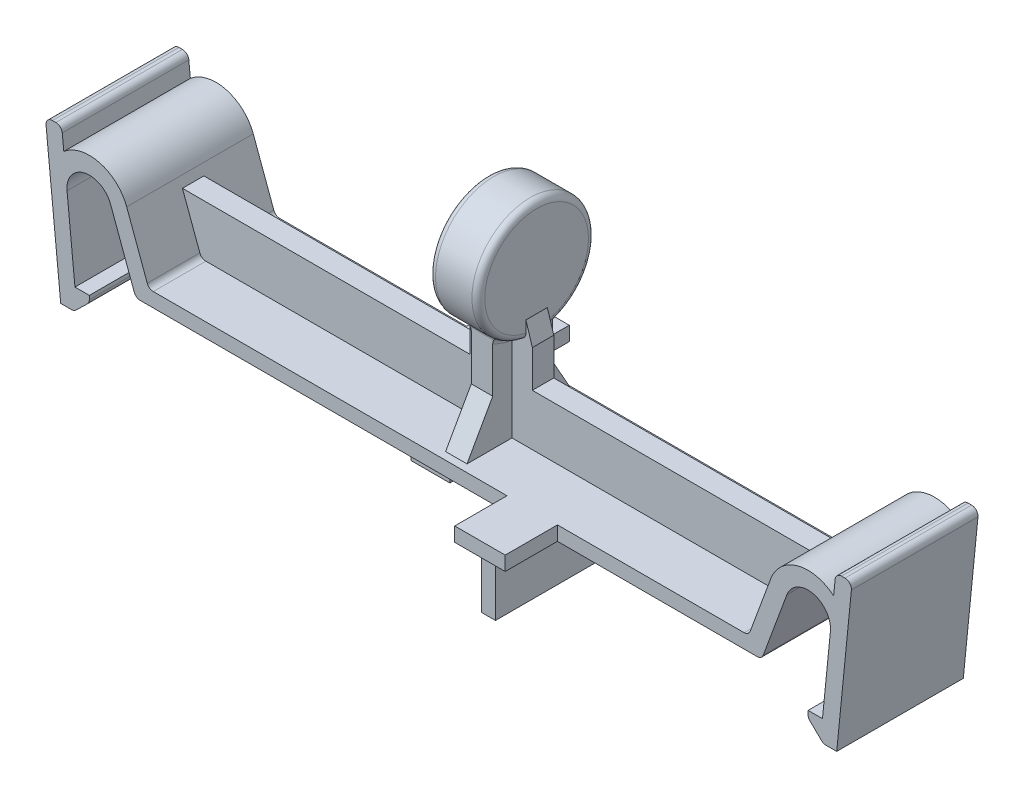
SolidWorks part; units mm, degrees
ref_plane "Front Plane" through (0, 0, 0) normal (0, 0, 1) x (1, 0, 0)
ref_plane "Top Plane" through (0, 0, 0) normal (0, 1, 0) x (1, 0, 0)
ref_plane "Right Plane" through (0, 0, 0) normal (1, 0, 0) x (0, 0, -1)
sketch "Sketch2" plane through (0, 0, 0) normal (0, 0, 1) x (1, 0, 0)
  line L3 (-37.5805, 8.6675) -> (-35.1807, 2.1508)
  line L4 (-34.477, 1.66) -> (34.477, 1.66)
  line L6 (35.997, 0) -> (-35.997, 0)
  line L7 (-36.7007, 0.4908) -> (-39.4573, 7.9764)
  line L12 (0, 0) -> (0, 8.4417) construction
  line L13 (-44.542, 6.8066) -> (-43.6179, -2.46)
  line L14 (-43.6179, -2.46) -> (-41.94, -2.46)
  line L15 (-41.94, -2.46) -> (-41.94, -2.8931)
  line L16 (-42.1673, -3.4309) -> (-43.5017, -4.7278)
  line L17 (-44.0244, -4.94) -> (-45.28, -4.94)
  line L18 (-45.28, -4.94) -> (-46.9928, 12.2356)
  line L19 (-46.2465, 13.06) -> (-45.8445, 13.06)
  line L20 (-45.0982, 12.3844) -> (-44.9201, 10.5982)
  line L21 (45.0982, 12.3844) -> (44.9201, 10.5982)
  line L22 (46.2465, 13.06) -> (45.8445, 13.06)
  line L23 (45.28, -4.94) -> (46.9928, 12.2356)
  line L24 (44.0244, -4.94) -> (45.28, -4.94)
  line L25 (42.1673, -3.4309) -> (43.5017, -4.7278)
  line L26 (41.94, -2.46) -> (41.94, -2.8931)
  line L27 (43.6179, -2.46) -> (41.94, -2.46)
  line L28 (44.542, 6.8066) -> (43.6179, -2.46)
  line L29 (36.7007, 0.4908) -> (39.4573, 7.9764)
  line L30 (37.5805, 8.6675) -> (35.1807, 2.1508)
  arc A1 (-39.4573, 7.9764) -> (-44.542, 6.8066) centre (-41.9251, 7.0676) ccw
  arc A2 (-44.9201, 10.5982) -> (-37.5805, 8.6675) centre (-41.9251, 7.0676) cw
  arc A3 (-41.94, -2.8931) -> (-42.1673, -3.4309) centre (-42.69, -2.8931) cw
  arc A4 (-43.5017, -4.7278) -> (-44.0244, -4.94) centre (-44.0244, -4.19) cw
  arc A5 (-35.997, 0) -> (-36.7007, 0.4908) centre (-35.997, 0.75) cw
  arc A6 (-35.1807, 2.1508) -> (-34.477, 1.66) centre (-34.477, 2.41) ccw
  arc A7 (-45.8445, 13.06) -> (-45.0982, 12.3844) centre (-45.8445, 12.31) cw
  arc A8 (-46.9928, 12.2356) -> (-46.2465, 13.06) centre (-46.2465, 12.31) cw
  arc A9 (46.9928, 12.2356) -> (46.2465, 13.06) centre (46.2465, 12.31) ccw
  arc A10 (45.8445, 13.06) -> (45.0982, 12.3844) centre (45.8445, 12.31) ccw
  arc A11 (35.1807, 2.1508) -> (34.477, 1.66) centre (34.477, 2.41) cw
  arc A12 (35.997, 0) -> (36.7007, 0.4908) centre (35.997, 0.75) ccw
  arc A13 (43.5017, -4.7278) -> (44.0244, -4.94) centre (44.0244, -4.19) ccw
  arc A14 (41.94, -2.8931) -> (42.1673, -3.4309) centre (42.69, -2.8931) ccw
  arc A15 (44.9201, 10.5982) -> (37.5805, 8.6675) centre (41.9251, 7.0676) ccw
  arc A16 (39.4573, 7.9764) -> (44.542, 6.8066) centre (41.9251, 7.0676) cw
  point P22 (-41.94, -3.21)
  point P25 (-43.72, -4.94)
  point P28 (-36.52, 0)
  point P31 (-35, 1.66)
  point P36 (-47.075, 13.06)
  point P63 (0, 1.66)
  dimension "D15" = 0.75
  dimension "D1" = 1.66
  dimension "D2" = 70
  dimension "D3" = 2
  dimension "D4" = 8.5
  dimension "D5" = 73.04
  dimension "D6" = 90.56
  dimension "D7" = 3.34
  dimension "D8" = 2.48
  dimension "D9" = 4.94
  dimension "D10" = 0.75
  dimension "D11" = 1.78
  dimension "D12" = 94.15
  dimension "D13" = 18
  dimension "D14" = 1.9
extrude "Boss-Extrude1" add sketch "Sketch2" along normal mid plane 14.77
sketch "Sketch3" plane through (0, 0, 0) normal (1, 0, 0) x (0, 0, -1)
  line L0 (-7.385, 1.66) -> (7.385, 1.66) construction
  line L1 (-1.25, 1.66) -> (1.25, 1.66)
  line L2 (-1.25, 1.66) -> (-1.25, 7.66)
  line L3 (-1.25, 7.66) -> (1.25, 7.66)
  line L4 (1.25, 1.66) -> (1.25, 7.66)
  line L5 (0, 0) -> (0, 7.66) construction
  dimension "D1" = 2.5
  dimension "D2" = 6
extrude "Boss-Extrude2" add sketch "Sketch3" along normal up to next and the other way up to next
sketch "Sketch4" plane through (0, 0, 0) normal (1, 0, 0) x (0, 0, -1)
  line L0 (-6.5, 1.66) -> (-3.5, 7)
  line L1 (-7.385, 1.66) -> (-1.25, 1.66) construction
  line L2 (-3.5, 7) -> (-3.5, 15.66)
  line L3 (-3.5, 15.66) -> (3.5, 15.66)
  line L4 (3.5, 15.66) -> (3.5, 7)
  line L5 (3.5, 7) -> (6.5, 1.66)
  line L6 (1.25, 1.66) -> (7.385, 1.66) construction
  line L7 (6.5, 1.66) -> (-6.5, 1.66)
  line L8 (0, 0) -> (0, 15.66) construction
  dimension "D1" = 7
  dimension "D2" = 13
  dimension "D3" = 5.34
  dimension "D4" = 14
extrude "Boss-Extrude3" add sketch "Sketch4" along normal mid plane 2.5
sketch "Sketch5" plane through (0, 0, 1.25) normal (0, 0, 1) x (1, 0, 0)
  line L0 (-37.2095, 7.66) -> (-1.25, 7.66) construction
  line L1 (-3.625, 7.66) -> (3.625, 7.66)
  line L2 (-3.625, 7.66) -> (-3.625, 11.98)
  line L3 (-3.625, 11.98) -> (3.625, 11.98)
  line L4 (3.625, 7.66) -> (3.625, 11.98)
  line L5 (0, 11.98) -> (0, 0) construction
  dimension "D1" = 7.25
  dimension "D2" = 4.32
extrude "Boss-Extrude4" add sketch "Sketch5" against normal up to surface (2.5 mm away) up to face at (21.8889, 4.136, -1.25)
sketch "Sketch6" plane through (0, 0, 0) normal (1, 0, 0) x (0, 0, -1)
  line L0 (0, 0) -> (0, 18.9708) construction
  line L1 (-7.385, 0) -> (7.385, 0) construction
  line L2 (1.25, 2.1508) -> (7.385, 2.1508) construction
  circle A0 centre (0, 18.9708) radius 6.8
  dimension "D1" = 13.6
  dimension "D2" = 23.62
extrude "Boss-Extrude5" add sketch "Sketch6" along normal mid plane 5.75
fillet "Fillet1" radius 0.75 6 edges at (-1.25, 12.1708, 0) (0, 13.1407, -3.5) (1.25, 12.1708, 0) (0, 13.1407, 3.5) (-2.875, 18.9708, -6.8) (2.875, 18.9708, -6.8)
sketch "Sketch7" plane through (0, 1.66, 0) normal (0, 1, 0) x (1, 0, 0)
  line L0 (34.477, 7.385) -> (-34.477, 7.385) construction
  line L1 (-12.69, 7.385) -> (-6.8, 7.385)
  line L2 (-12.69, 7.385) -> (-12.69, 13.485)
  line L3 (-12.69, 13.485) -> (-6.8, 13.485)
  line L4 (-6.8, 7.385) -> (-6.8, 13.485)
  line L5 (34.477, -7.385) -> (-34.477, -7.385) construction
  line L6 (6.8, -7.385) -> (12.69, -7.385)
  line L7 (6.8, -7.385) -> (6.8, -13.485)
  line L8 (6.8, -13.485) -> (12.69, -13.485)
  line L9 (12.69, -7.385) -> (12.69, -13.485)
  line L10 (0, 0) -> (0, 21.6539) construction
  line L11 (6.8, 7.385) -> (12.69, 7.385) construction
  line L12 (6.8, 7.385) -> (6.8, 13.485) construction
  line L13 (6.8, 13.485) -> (12.69, 13.485) construction
  line L14 (12.69, 7.385) -> (12.69, 13.485) construction
  line L15 (-12.69, -7.385) -> (-6.8, -7.385) construction
  line L16 (-12.69, -7.385) -> (-12.69, -13.485) construction
  line L17 (-12.69, -13.485) -> (-6.8, -13.485) construction
  line L18 (-6.8, -7.385) -> (-6.8, -13.485) construction
  line L19 (0, 0) -> (-21.3163, 0) construction
  dimension "D1" = 6.1
  dimension "D2" = 5.89
  dimension "D3" = 6.8
extrude "Boss-Extrude6" add sketch "Sketch7" against normal up to surface (1.66 mm away) up to face at (0, 0, 0)
sketch "Sketch8" plane through (0, 0, 0) normal (0, -1, 0) x (1, 0, 0)
  line L0 (10.555, 12.485) -> (10.555, -1.25)
  line L1 (1.25, -1.25) -> (34.477, -1.25) construction
  line L2 (10.555, -1.25) -> (-8.935, -1.25)
  line L3 (-34.477, -1.25) -> (-1.25, -1.25) construction
  line L4 (-8.935, -1.25) -> (-8.935, -12.485)
  line L5 (-8.935, -12.485) -> (-10.555, -12.485)
  line L6 (-10.555, -12.485) -> (-10.555, 1.25)
  line L7 (-34.477, 1.25) -> (-1.25, 1.25) construction
  line L8 (-10.555, 1.25) -> (8.935, 1.25)
  line L9 (1.25, 1.25) -> (34.477, 1.25) construction
  line L10 (8.935, 1.25) -> (8.935, 12.485)
  line L11 (8.935, 12.485) -> (10.555, 12.485)
  line L12 (9.745, 12.485) -> (9.745, 13.485) construction
  line L13 (12.69, 13.485) -> (6.8, 13.485) construction
  line L14 (-9.745, -12.485) -> (-9.745, -13.485) construction
  line L15 (-12.69, -13.485) -> (-6.8, -13.485) construction
  dimension "D1" = 1.62
  dimension "D2" = 1
extrude "Boss-Extrude7" add sketch "Sketch8" along normal blind 6.52
sketch "Sketch9" plane through (0, 0, 1.25) normal (0, 0, 1) x (1, 0, 0)
  line L0 (8.935, -6.52) -> (-10.555, -6.52) construction
  line L1 (6, -6.52) -> (-6, -6.52)
  line L2 (6, -6.52) -> (6, -2.52)
  line L3 (6, -2.52) -> (-6, -2.52)
  line L4 (-6, -6.52) -> (-6, -2.52)
  line L5 (0, 0) -> (0, -6.52) construction
  dimension "D1" = 12
  dimension "D2" = 4
extrude "Cut-Extrude1" cut sketch "Sketch9" against normal through all both and the other way through all
sketch "Sketch11" plane through (0, 0, 1.25) normal (0, 0, 1) x (1, 0, 0)
  line L0 (-3.625, 11.98) -> (-2.875, 14.4022)
  line L1 (-2.875, 25.0208) -> (-2.875, 12.9208) construction
  line L2 (-2.875, 14.4022) -> (2.875, 14.4022)
  line L3 (2.875, 12.9208) -> (2.875, 25.0208) construction
  line L4 (2.875, 14.4022) -> (3.625, 11.98)
  line L5 (3.625, 11.98) -> (-3.625, 11.98)
  dimension "D1" = 2.4222
extrude "Boss-Extrude8" add sketch "Sketch11" against normal up to surface (2.5 mm away) up to face at (-14.7565, 7.0203, -1.25)
